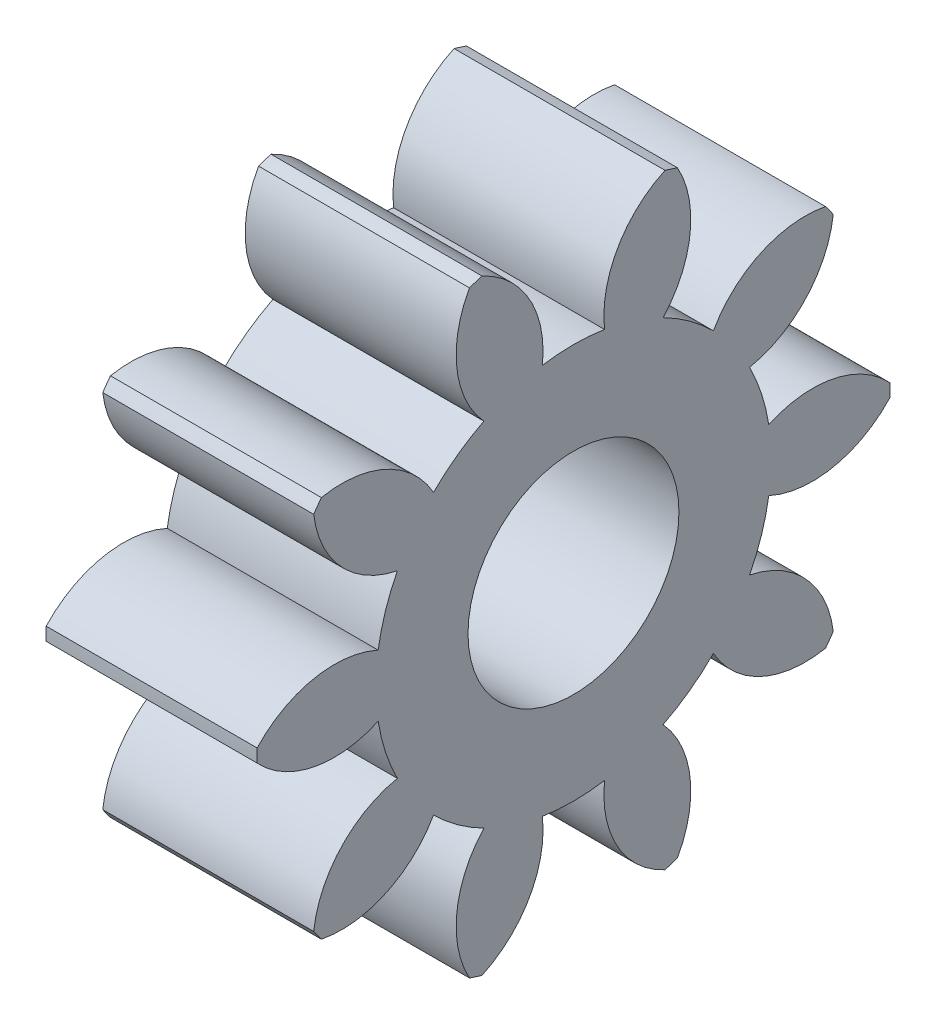
SolidWorks part; units mm, degrees
ref_plane "Plane1" through (0, 0, 0) normal (0, 0, 1) x (1, 0, 0)
ref_plane "Plane2" through (0, 0, 0) normal (0, 1, 0) x (1, 0, 0)
ref_plane "Plane3" through (0, 0, 0) normal (1, 0, 0) x (0, 0, -1)
sketch "HoldingSke" plane through (0, 0, 0) normal (0, 1, 0) x (1, 0, 0)
  line L0 (0, 0) -> (0.6565, -0.1158)
  line L1 (-15, 0) -> (100, 0) construction
  line L2 (0, 0) -> (-2.1039, 2.3779)
  line L3 (0, 0) -> (-11.863, 4.5341)
  line L4 (0, 0) -> (8.5048, 1.4996)
  line L5 (0, 0) -> (-46.8476, -17.4728)
  line L6 (0, 0) -> (-9.9476, -6.7116)
  line L7 (-2.1039, 2.3779) -> (8.6586, 51.2059)
  line L8 (-76.2, 54.61) -> (-76.1, 54.61)
  line L9 (-71.009, 38.7566) -> (-53.1078, 45.2721)
  line L10 (-76.2, 71.12) -> (104.1128, 71.12)
  line L11 (0, 0) -> (-12, 0)
  line L12 (-76.2, 101.6) -> (-76.147, 101.6)
  line L13 (24.9733, 27.94) -> (52.9518, 28.4284)
  line L14 (24.9733, 27.94) -> (24.9743, 27.94)
  line L15 (24.9733, 27.94) -> (100.4006, 29.5858)
  line L16 (-63.627, -1.5) -> (-12.827, -1.5)
  circle A0 centre (0, 0) radius 0.4
  circle A1 centre (0, 0) radius 5.624
  circle A2 centre (0, 0) radius 37.5
  circle A3 centre (0, 0) radius 0.4
  dimension "MHD" = 11.248
  dimension "Hub_dia" = 75
  dimension "Bore" = 0.8
  dimension "MBD" = 0.8
  dimension "Num_teeth" = 10
  dimension "Pitch_radius" = 180.3128
  dimension "Pitch" = 0.6667
  dimension "Width" = 12
  dimension "Overall_len" = 50
  dimension "Show_teeth" = 10
  dimension "Thickness" = 12
  dimension "OAL" = 50.0001
  dimension "T_dim" = 0.1
  dimension "Ap" = 20
  dimension "H" = 19.05
  dimension "Backlash" = 0.053
  dimension "Addendum_fac" = 1
  dimension "Dedendum_fac" = 1.25
  dimension "Clearance_fac" = 0.25
  dimension "Dedendum_add" = 0.001
  dimension "Module" = 1.5
sketch "BasProSke" plane through (0, 0, 0) normal (0, 1, 0) x (1, 0, 0)
  line L0 (-10, 0) -> (60, 0) construction
  line L1 (0, 0) -> (0, 9)
  line L2 (0, 0) -> (12, 0)
  line L3 (12, 0) -> (12, 9)
  line L4 (12, 9) -> (0, 9)
  dimension "Diameter" = 18
  dimension "Thickness" = 12
revolve "Base-Revolve" add sketch "BasProSke" angle 360 about L0
sketch "TooCutSke" plane through (0, 0, 0) normal (1, 0, 0) x (0, 0, -1)
  line L1 (0, 0) -> (0, 107) construction
  line L2 (0, 0) -> (-1.2658, 7.3924) construction
  line L3 (0, 0) -> (-4.5869, 14.117) construction
  line L4 (-1.2658, 7.3924) -> (-2.2934, 7.0585) construction
  arc A0 (0.8839, 5.5541) -> (-0.8839, 5.5541) centre (0, 0) ccw
  arc A1 (2.6378, 8.6313) -> (-2.6378, 8.6313) centre (0, 0) ccw
  circle A2 centre (0, 0) radius 7.5 construction
  circle A3 centre (0, 0) radius 7.0477 construction
  arc A4 (-0.8839, 5.5541) -> (-2.6378, 8.6313) centre (-3.8646, 5.8936) ccw
  arc A5 (2.6378, 8.6313) -> (0.8839, 5.5541) centre (3.8646, 5.8936) ccw
  dimension "Root_dia" = 11.248
  dimension "Overcut_dia" = 18.0508
  dimension "Pitch_dia" = 15
  dimension "Base_dia" = 14.0954
  dimension "Flank_rad" = 3
  dimension "Half_ang" = 18
  dimension "Half_CT" = 1.0805
extrude "ToothCut" cut sketch "TooCutSke" along normal through all
fillet "Breaks" [suppressed] radius 0.03 tangent propagation no
fillet "RootFillets" [suppressed] radius 0.376
pattern_circular "TeethCuts" count 10 every 36 about axis through (-10, 0, 0) along (1, 0, 0) of "ToothCut", "RootFillets", "Breaks"
sketch "HubNeaOneSke" plane through (0, 0, 0) normal (-1, 0, 0) x (0, 0, 1)
  circle A0 centre (0, 0) radius 5.624
  dimension "Diameter" = 11.248
extrude "HubNearOne" [suppressed] add sketch "HubNeaOneSke" along normal blind 38.0001
sketch "HubNeaBotSke" plane through (0, 0, 0) normal (-1, 0, 0) x (0, 0, 1)
  circle A0 centre (0, 0) radius 5.624
  dimension "Diameter" = 11.248
extrude "HubNearBoth" [suppressed] add sketch "HubNeaBotSke" along normal blind 19
ref_plane "FarPln" through (12, 0, 0) normal (1, 0, 0) x (0, 0, -1)
sketch "HubFarSke" plane through (12, 0, 0) normal (1, 0, 0) x (0, 0, -1)
  circle A0 centre (0, 0) radius 5.624
  dimension "Diameter" = 11.248
extrude "HubFar" [suppressed] add sketch "HubFarSke" along normal blind 19
sketch "BorSke" plane through (0, 0, 0) normal (1, 0, 0) x (0, 0, -1)
  circle A0 centre (0, 0) radius 0.4
  dimension "Diameter" = 0.8
extrude "Bore" cut sketch "BorSke" along normal mid plane 100.0001
sketch "KeySke" plane through (0, 0, 0) normal (1, 0, 0) x (0, 0, -1)
  line L0 (-0.05, 0) -> (-0.05, 0.5)
  line L1 (-0.05, 0.5) -> (0.05, 0.5)
  line L2 (0.05, 0.5) -> (0.05, 0)
  line L3 (0, 0) -> (0, 34) construction
  line L4 (-0.05, 0) -> (0.05, 0)
  dimension "Offset" = 0.5
  dimension "Width" = 0.1
extrude "Keyway" [suppressed] cut sketch "KeySke" along normal mid plane 100.0001
pattern_circular "Keyway2" [suppressed] count 2 every 90 about axis through (-10, 0, 0) along (1, 0, 0)
sketch "Sketch1" plane through (0, 0, 0) normal (-1, 0, 0) x (0, 0, 1)
  circle A0 centre (0, 0) radius 3
  circle M41 centre (0, 0) radius 0.4
  dimension "D1" = 6
extrude "Cut-Extrude2" cut sketch "Sketch1" against normal through all contours A0 M41 region at (0, 0, -2.9151)
fillet "Fillet1" [suppressed] radius 0.5
sketch "Sketch2" plane through (12, 0, 0) normal (1, 0, 0) x (0, 0, -1)
  circle A0 centre (0, 0) radius 20.4408
extrude "Cut-Extrude3" cut sketch "Sketch2" against normal offset from surface (6 mm away) 6 up to face at (0, 0, 3)
equation "' \"Module@HoldingSke\" = 6.35"
equation "' \"Num_teeth@HoldingSke\" = 12"
equation "' \"Ap@HoldingSke\" =  20"
equation "' \"Width@HoldingSke\" = 0.5 * 25.4"
equation "' \"Hub_dia@HoldingSke\"= 1 * 25.4"
equation "' \"Overall_len@HoldingSke\" = 1.0 * 25.4"
equation "' \"Bore@HoldingSke\" = 0.75 * 25.4"
equation "' \"T_dim@HoldingSke\" = 0.1 * 25.4"
equation "' \"Width@KeySke\" = 0.25 * 25.4"
equation "' \"Show_teeth@HoldingSke\" = 13"
equation "' \"Backlash@HoldingSke\" = 0.009 * 25.4"
equation "' \"Addendum_fac@HoldingSke\" = 1.0"
equation "' \"Dedendum_fac@HoldingSke\" = 1.25"
equation "' \"Dedendum_add@HoldingSke\" = 0.00005 * 25.4"
equation "' \"Clearance_fac@HoldingSke\" = 0.25"
equation "\"Pitch@HoldingSke\" = 1 / \"Module@HoldingSke\""
equation "\"Overcut_dia@TooCutSke\" = (\"Num_teeth@HoldingSke\" + 2 * \"Addendum_fac@HoldingSke\") / \"Pitch@HoldingSke\" + 0.002 * 25.4"
equation "\"Pitch_dia@TooCutSke\" = \"Num_teeth@HoldingSke\" / \"Pitch@HoldingSke\""
equation "\"Base_dia@TooCutSke\" = \"Num_teeth@HoldingSke\" / \"Pitch@HoldingSke\" * cos((\"Ap@HoldingSke\"  * 3.14159265 / 180))"
equation "\"Root_dia@TooCutSke\" = (\"Num_teeth@HoldingSke\" + 2) / \"Pitch@HoldingSke\" - 2 * (\"Addendum_fac@HoldingSke\" + \"Dedendum_fac@HoldingSke\") / \"Pitch@HoldingSke\" - \"Dedendum_add@HoldingSke\" * 2"
equation "\"Half_ang@TooCutSke\" = 180 / \"Num_teeth@HoldingSke\""
equation "\"Half_CT@TooCutSke\" = \"Num_teeth@HoldingSke\" / \"Pitch@HoldingSke\" * sin((3.14159265 / 2 / \"Num_teeth@HoldingSke\")) / 2 - 7 * \"Backlash@HoldingSke\" / 4"
equation "\"Flank_rad@TooCutSke\" = \"Num_teeth@HoldingSke\" / \"Pitch@HoldingSke\" / 5"
equation "\"Radius@RootFillets\" = \"Clearance_fac@HoldingSke\" / \"Pitch@HoldingSke\" + \"Dedendum_add@HoldingSke\""
equation "\"Break_rad@Breaks\" = 0.02 / \"Pitch@HoldingSke\""
equation "\"Thickness@HoldingSke\" = \"Width@HoldingSke\""
equation "\"OAL@HoldingSke\" = \"Thickness@HoldingSke\""
equation "\"MHD@HoldingSke\" = (\"Num_teeth@HoldingSke\" + 2) / \"Pitch@HoldingSke\" - 2 * (\"Addendum_fac@HoldingSke\" + \"Dedendum_fac@HoldingSke\")  / \"Pitch@HoldingSke\" - \"Dedendum_add@HoldingSke\" * 2"
equation "\"MBD@HoldingSke\" = (\"Num_teeth@HoldingSke\" + 2) / \"Pitch@HoldingSke\" - 2 * (\"Addendum_fac@HoldingSke\" + \"Dedendum_fac@HoldingSke\")  / \"Pitch@HoldingSke\" - \"Dedendum_add@HoldingSke\" * 2 - 0.002 * 25.4"
equation "\"MHD@HoldingSke\" = ((sgn( \"MHD@HoldingSke\" - \"Hub_dia@HoldingSke\" )-1)*( \"MHD@HoldingSke\" - \"Hub_dia@HoldingSke\" ))/-2+ \"Hub_dia@HoldingSke\""
equation "\"MBD@HoldingSke\" = ((sgn( \"MBD@HoldingSke\" - \"Bore@HoldingSke\" )-1)*( \"MBD@HoldingSke\" - \"Bore@HoldingSke\" ))/-2+ \"Bore@HoldingSke\""
equation "\"OAL@HoldingSke\" = ((sgn( \"OAL@HoldingSke\" - \"Overall_len@HoldingSke\" )+1)*( \"OAL@HoldingSke\" - \"Overall_len@HoldingSke\" ))/2 + \"Overall_len@HoldingSke\" + 0.000002 * 25.4"
equation "\"Num_teeth@TeethCuts\" = int( \"Show_teeth@HoldingSke\" ) + 1"
equation "\"Num_teeth@TeethCuts\" = ((sgn( \"Num_teeth@TeethCuts\" - \"Num_teeth@HoldingSke\" )-1)*( \"Num_teeth@TeethCuts\" - \"Num_teeth@HoldingSke\" ))/-2+ \"Num_teeth@HoldingSke\""
equation "\"Num_teeth@TeethCuts\" = ((sgn( \"Num_teeth@TeethCuts\" - 2.0)+1)*( \"Num_teeth@TeethCuts\" - 2.0))/2 +2.0"
equation "\"Angle@TeethCuts\" = 360.0 / \"Num_teeth@HoldingSke\""
equation "\"Diameter@BasProSke\" = (\"Num_teeth@HoldingSke\" + 2 * \"Addendum_fac@HoldingSke\") / \"Pitch@HoldingSke\""
equation "\"Thickness@BasProSke\"  = \"Thickness@HoldingSke\""
equation "' \"Fillet_rad@BasProSke\" =  \"Thickness@HoldingSke\" * 0.05"
equation "\"MHD@HoldingSke\" = ((sgn( \"MHD@HoldingSke\" - \"Root_dia@TooCutSke\" )-1)*( \"MHD@HoldingSke\" - \"Root_dia@TooCutSke\" ))/-2+ \"Root_dia@TooCutSke\""
equation "\"Diameter@HubNeaOneSke\" = \"MHD@HoldingSke\""
equation "\"Length@HubNearOne\" = \"OAL@HoldingSke\" - \"Thickness@BasProSke\""
equation "\"Diameter@HubNeaBotSke\" = \"MHD@HoldingSke\""
equation "\"Length@HubNearBoth\" = ( \"OAL@HoldingSke\" - \"Thickness@BasProSke\" ) / 2.0"
equation "\"Thickness@FarPln\" = \"Thickness@BasProSke\""
equation "\"Diameter@HubFarSke\" = \"MHD@HoldingSke\""
equation "\"Length@HubFar\" = ( \"OAL@HoldingSke\" - \"Thickness@BasProSke\" ) / 2.0"
equation "\"Diameter@BorSke\" = \"MBD@HoldingSke\""
equation "\"D1@Bore\" = \"OAL@HoldingSke\" * 2.0"
equation "\"D1@Keyway\" = \"OAL@HoldingSke\" * 2.0"
equation "\"Offset@KeySke\" = \"T_dim@HoldingSke\" + \"MBD@HoldingSke\" / 2.0"
